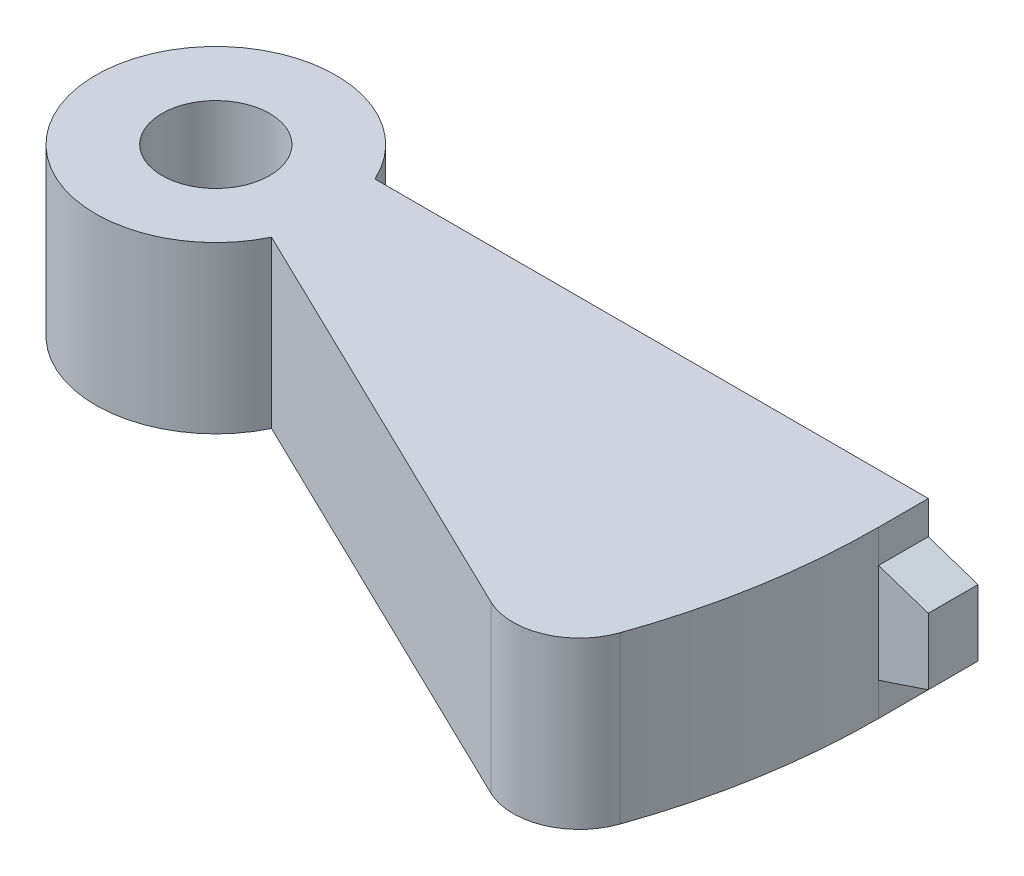
SolidWorks part; units mm, degrees
ref_plane "Front Plane" through (0, 0, 0) normal (0, 0, 1) x (1, 0, 0)
ref_plane "Top Plane" through (0, 0, 0) normal (0, 1, 0) x (1, 0, 0)
ref_plane "Right Plane" through (0, 0, 0) normal (1, 0, 0) x (0, 0, -1)
sketch "Sketch1" plane through (0, 0, 0) normal (0, 1, 0) x (1, 0, 0)
  line L0 (0, 0) -> (20, 0)
  line L1 (16.0985, -7.7999) -> (0, 0)
  line L2 (15.7784, -8) -> (20.804, -8) construction
  arc A0 (20, 0) -> (18.8562, -6.6667) centre (0, 0) cw
  arc A1 (18.8562, -6.6667) -> (16.0985, -7.7999) centre (16.9706, -6) cw
  dimension "D1" = 20
  dimension "D3" = 2
  dimension "D2" = 8
extrude "Boss-Extrude1" add sketch "Sketch1" against normal mid plane 5 contours L1 L0 A0 A1
shell "Shell1" [suppressed] thickness 1.5
sketch "Sketch2" plane through (0, 0, 0) normal (0, 1, 0) x (1, 0, 0)
  circle A0 centre (0, 0) radius 3.625
  circle A1 centre (0, 0) radius 1.625
  dimension "D1" = 2
  dimension "D2" = 3.25
sketch "Sketch3" plane through (0, 0, 0) normal (0, 0, -1) x (-1, 0, 0)
  line L0 (-20, -2.5) -> (-20, -1.5)
  line L1 (0, 2.5) -> (-20, 2.5)
  line L2 (0, 2.5) -> (0, -2.5)
  line L3 (0, -2.5) -> (-20, -2.5)
  line L5 (-20, -2.5) -> (-20, 2.5) construction
  line L6 (-20, -1.5) -> (-21.5, -1)
  line L7 (-21.5, -1) -> (-21.5, 1)
  line L8 (-21.5, 1) -> (-20, 1.5)
  line L9 (-20, 1.5) -> (-20, 2.5)
  dimension "D1" = 1.5
  dimension "D2" = 2
  dimension "D3" = 3
extrude "Boss-Extrude2" add sketch "Sketch3" along normal blind 1.5 contours L3 L0 L6 L7 L8 L9 L1 L2
extrude "Boss-Extrude3" add sketch "Sketch2" along normal up to surface and the other way up to surface up to face at (12.582, 2.5, 2.022) other way up to face at (12.582, -2.5, 2.022)
extrude "Cut-Extrude1" cut sketch "Sketch2<2>" against normal through all both and the other way through all contours A1 region at (0, 0, 0)
sketch "Sketch2<2>" plane through (0, 0, 0) normal (0, 1, 0) x (1, 0, 0) same geometry as "Sketch2"
